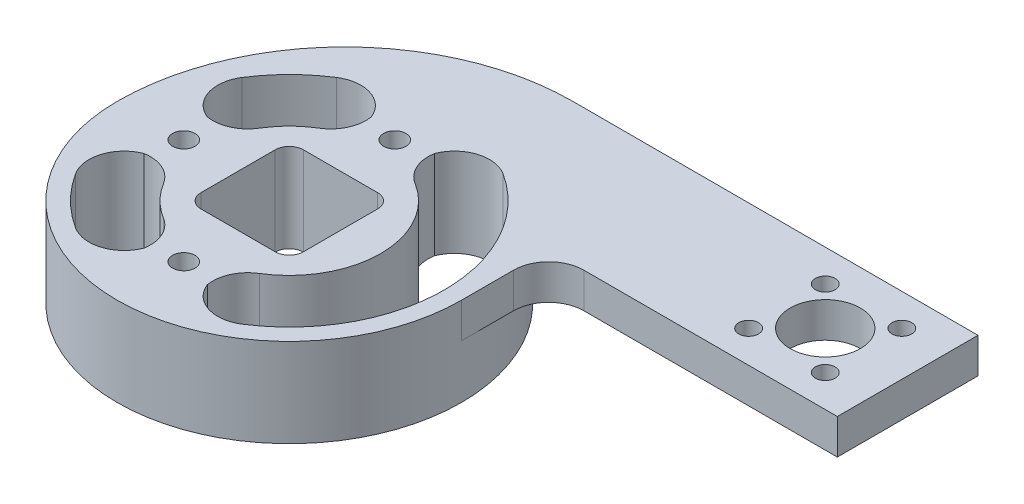
SolidWorks part; units mm, degrees
material "6061-T6 (SS)"
ref_plane "Front Plane" through (0, 0, 0) normal (0, 0, 1) x (1, 0, 0)
ref_plane "Top Plane" through (0, 0, 0) normal (0, 1, 0) x (1, 0, 0)
ref_plane "Right Plane" through (0, 0, 0) normal (1, 0, 0) x (0, 0, -1)
sketch "Sketch1" plane through (0, 0, 0) normal (0, 1, 0) x (1, 0, 0)
  line L0 (-1.1049, 0) -> (-31.0896, 0) construction
  line L1 (-1.1049, 0) -> (31.0896, 0) construction
  circle A0 centre (0, 0) radius 31.0896
  dimension "D1" = 62.1792
extrude "Boss-Extrude1" add sketch "Sketch1" along normal blind 16.002
sketch "Sketch2" plane through (0, 16.002, 0) normal (0, 1, 0) x (1, 0, 0)
  line L0 (0, 0) -> (-31.0896, 0) construction
  line L1 (0, 0) -> (31.0896, 0) construction
  line L2 (-31.0896, 0) -> (-31.0896, 41.148)
  line L3 (-31.0896, 41.148) -> (83.2104, 41.148)
  line L4 (83.2104, 41.148) -> (83.2104, 15.748)
  line L5 (31.0896, 0) -> (31.0896, 15.748)
  line L6 (31.0896, 15.748) -> (83.2104, 15.748)
  circle A0 centre (0, 0) radius 31.0896 construction
  circle A2 centre (0, 0) radius 31.0896
  arc A3 (-31.0896, 0) -> (31.0896, 0) centre (0, 0) ccw
  dimension "D1" = 0
  dimension "D2" = 114.3
  dimension "D3" = 25.4
  dimension "D4" = 15.748
extrude "Boss-Extrude2" add sketch "Sketch2" against normal blind 6.35
fillet "Fillet1" [suppressed] radius 6.35
fillet "Fillet2" radius 6.35 1 edges at (31.0896, 12.827, -15.748)
sketch "Sketch4" plane through (0, 16.002, 0) normal (0, 1, 0) x (1, 0, 0)
  line L0 (83.2104, 41.148) -> (58.166, 41.148) construction
  line L1 (83.2104, 41.148) -> (-31.0896, 41.148) construction
  line L2 (58.166, 41.148) -> (58.166, 28.448) construction
  line L3 (58.166, 28.448) -> (78.486, 28.448) construction
  line L4 (68.326, 28.448) -> (75.2408, 35.3628) construction
  line L5 (68.326, 28.448) -> (75.2408, 21.5332) construction
  line L6 (68.326, 28.448) -> (61.4112, 21.5332) construction
  line L7 (68.326, 28.448) -> (61.4112, 35.3628) construction
  circle A0 centre (61.4112, 35.3628) radius 1.778
  circle A1 centre (75.2408, 35.3628) radius 1.778
  circle A2 centre (75.2408, 21.5332) radius 1.778
  circle A3 centre (68.326, 28.448) radius 6.35
  circle A4 centre (61.4112, 21.5332) radius 1.778
extrude "Cut-Extrude2" cut sketch "Sketch4" against normal up to next
sketch "Sketch5" plane through (0, 16.002, 0) normal (0, 1, 0) x (1, 0, 0)
  line L1 (9.2497, 9.2497) -> (-9.2497, 9.2497)
  line L2 (9.2497, 9.2497) -> (9.2497, -9.2497)
  line L3 (9.2497, -9.2497) -> (-9.2497, -9.2497)
  line L4 (-9.2497, 9.2497) -> (-9.2497, -9.2497)
  line L5 (9.2497, 9.2497) -> (-9.2497, -9.2497) construction
  line L6 (9.2497, -9.2497) -> (-9.2497, 9.2497) construction
  point P0 (0, 0)
  dimension "D1" = 26.162
extrude "Cut-Extrude3" cut sketch "Sketch5" against normal up to next
fillet "Fillet3" radius 2.54 1 edges at (-9.2497, 8.001, -9.2497)
fillet "Fillet4" radius 2.54 1 edges at (9.2497, 8.001, -9.2497)
fillet "Fillet5" radius 2.54 1 edges at (9.2497, 8.001, 9.2497)
fillet "Fillet6" radius 2.54 1 edges at (-9.2497, 8.001, 9.2497)
sketch "Sketch7" plane through (0, 0, 0) normal (0, 1, 0) x (1, 0, 0)
  line L0 (0, 27.94) -> (0, -31.0896)
  line L1 (0, 0) -> (-7.4507, 26.9283)
  line L2 (-7.4507, -26.9283) -> (0, 0)
  line L3 (0, 0) -> (7.4507, 26.9283)
  line L4 (0, 0) -> (7.4507, -26.9283)
  line L5 (-26.9283, 7.4507) -> (0, 0)
  line L6 (0, 0) -> (26.9283, -7.4507) construction
  line L7 (-26.9283, -7.4507) -> (0, 0)
  line L8 (0, 0) -> (26.9283, 7.4507) construction
  line L9 (0, 0) -> (-26.2234, 0) construction
  circle A0 centre (0, 0) radius 16.51
  circle A1 centre (0, 0) radius 27.94
  circle A2 centre (0, 0) radius 31.0896 construction
  circle A3 centre (-19.05, 0) radius 2.0193
  circle A4 centre (0, 19.05) radius 2.0193
  circle A5 centre (0, -19.05) radius 2.0193
  circle A6 centre (0, 0) radius 19.05 construction
  dimension "D1" = 33.02
  dimension "D2" = 55.88
  dimension "D3" = 4.0386
  dimension "D4" = 38.1
  dimension "D5" = 5.08
  dimension "D6" = 5.08
  dimension "D7" = 5.08
  dimension "D8" = 5.08
extrude "Cut-Extrude4" cut sketch "Sketch7" along normal through all contours L4 A1 L3 A0 | L7 A1 L2 A0 | L1 A1 L5 A0 | A3 | A5 | A4 region at (16.8291, 0, 0) region at (-15.3599, 0, -15.3599) region at (-15.3599, 0, 15.3599)
fillet "Fillet7" radius 6.35 12 edges at (-26.9283, 8.001, -7.4507) (-7.4507, 8.001, -26.9283) (-4.4027, 8.001, -15.9122) (4.4027, 8.001, -15.9122) (7.4507, 8.001, -26.9283) (4.4027, 8.001, 15.9122) (7.4507, 8.001, 26.9283) (-7.4507, 8.001, 26.9283) (-4.4027, 8.001, 15.9122) (-15.9122, 8.001, 4.4027) (-26.9283, 8.001, 7.4507) (-15.9122, 8.001, -4.4027)
fillet "Fillet8" radius 41.148 1 edges at (-31.0896, 12.827, -41.148)
